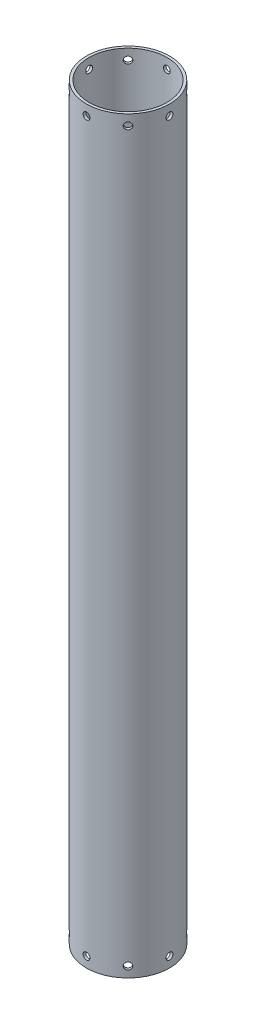
SolidWorks part; units mm, degrees
material "6061-T6 (SS)"
ref_plane "Front Plane" through (0, 0, 0) normal (0, 0, 1) x (1, 0, 0)
ref_plane "Top Plane" through (0, 0, 0) normal (0, 1, 0) x (1, 0, 0)
ref_plane "Right Plane" through (0, 0, 0) normal (1, 0, 0) x (0, 0, -1)
sketch "Sketch1" plane through (0, 0, 0) normal (0, 1, 0) x (1, 0, 0)
  circle A0 centre (0, 0) radius 50.8
  circle A1 centre (0, 0) radius 47.625
  dimension "D1" = 101.6
  dimension "D2" = 95.25
extrude "Boss-Extrude1" add sketch "Sketch1" along normal blind 914.4
ref_plane "Plane1" through (0, 0, 50.8) normal (0, 0, 1) x (1, 0, 0)
hole_wizard "21/64 (0.32813) Diameter Hole1" positions "Sketch2" profile "Sketch3" hole size "21/64" standard "ANSI Inch"
sketch "Sketch2" plane through (0, 0, 50.8) normal (0, 0, 1) x (1, 0, 0)
  line L0 (47.625, 914.4) -> (-47.625, 914.4) construction
  point P0 (0, 12.7)
  point P2 (0, 901.7)
  dimension "D1" = 12.7
  dimension "D2" = 12.7
sketch "Sketch3" plane through (0, 12.7, 50.8) normal (1, 0, 0) x (0, -1, 0)
  line L0 (0, 0) -> (0, 7.62)
  line L1 (0, 7.62) -> (4.1673, 5.1161)
  line L2 (4.1673, 5.1161) -> (4.1673, 0)
  line L5 (4.1673, 0) -> (0, 0)
  line L10 (0, 7.62) -> (-4.1673, 5.1161) construction
  line L11 (0, -6.35) -> (0, 107.95) construction
  dimension "Hole Dia." = 8.3345
  dimension "Hole Depth" = 7.62
  dimension "Drill Angle" = 118
pattern_circular "CirPattern1" count 8 over 360 about axis through (0, 914.4, 0) along (0, -1, 0) of "21/64 (0.32813) Diameter Hole1"
ref_plane "Plane2" through (0, 0, -50.8) normal (0, 0, -1) x (-1, 0, 0)
hole_wizard "Ø1.2 (1.2) Diameter Hole1" positions "Sketch7" profile "Sketch8" hole size "Ø1.2" standard "ANSI Metric" end condition up to next
sketch "Sketch7" plane through (0, 0, -50.8) normal (0, 0, -1) x (-1, 0, 0)
  line L0 (0, 914.4) -> (0, 552.45)
  line L1 (47.625, 914.4) -> (-47.625, 914.4) construction
  point P0 (0, 552.45)
  dimension "D1" = 361.95
sketch "Sketch8" plane through (0, 552.45, -50.8) normal (1, 0, 0) x (0, 1, 0)
  line L0 (0, 0) -> (0, 3.175)
  line L1 (0, 3.175) -> (0.6, 3.175)
  line L2 (0.6, 3.175) -> (0.6, 0)
  line L5 (0.6, 0) -> (0, 0)
  line L11 (0, -6.35) -> (0, 107.95) construction
  dimension "Thru Hole Dia." = 1.2
  dimension "Thru Hole Depth" = 3.175
